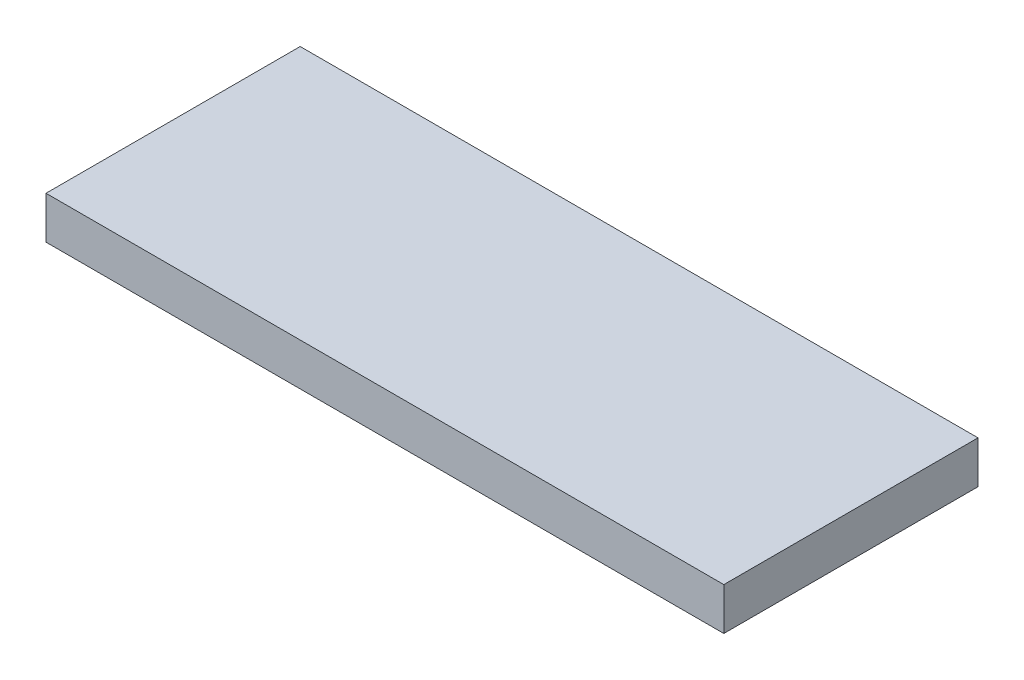
SolidWorks part; units mm, degrees
ref_plane "Front Plane" through (0, 0, 0) normal (0, 0, 1) x (1, 0, 0)
ref_plane "Top Plane" through (0, 0, 0) normal (0, 1, 0) x (1, 0, 0)
ref_plane "Right Plane" through (0, 0, 0) normal (1, 0, 0) x (0, 0, -1)
ref_axis "X" through (-88.99, 0, 0) along (1, 0, 0)
ref_axis "Y" through (0, 55, 0) along (0, -1, 0)
ref_axis "Z" through (0, 0, -88.99) along (0, 0, 1)
sketch "Sketch1" plane through (0, 0, 0) normal (0, 1, 0) x (1, 0, 0)
  line L1 (-80, 30) -> (80, 30)
  line L2 (-80, 30) -> (-80, -30)
  line L3 (-80, -30) -> (80, -30)
  line L4 (80, 30) -> (80, -30)
  line L5 (-80, 30) -> (80, -30) construction
  line L6 (-80, -30) -> (80, 30) construction
  point P0 (0, 0)
  dimension "D1" = 60
  dimension "D2" = 160
extrude "Boss-Extrude1" add sketch "Sketch1" against normal blind 10
